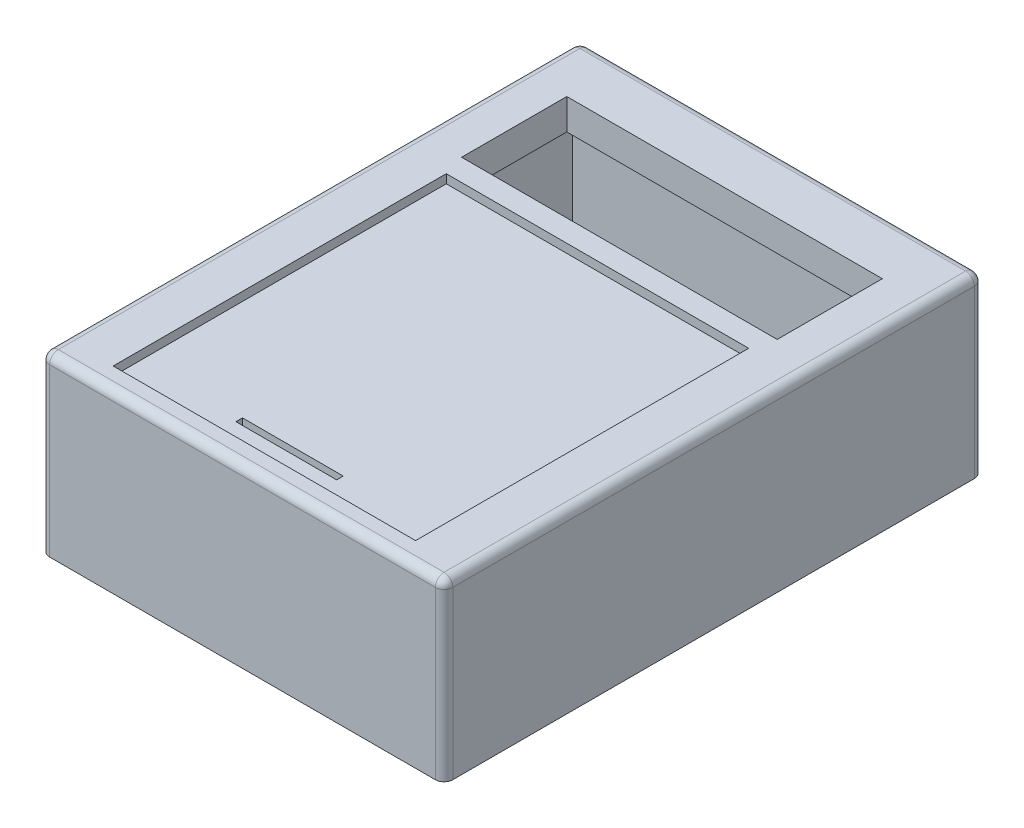
SolidWorks part; units mm, degrees
ref_plane "Front Plane" through (0, 0, 0) normal (0, 0, 1) x (1, 0, 0)
ref_plane "Top Plane" through (0, 0, 0) normal (0, 1, 0) x (1, 0, 0)
ref_plane "Right Plane" through (0, 0, 0) normal (1, 0, 0) x (0, 0, -1)
sketch "Sketch1" plane through (0, 0, 0) normal (0, 1, 0) x (1, 0, 0)
  line L1 (0, 0) -> (92, 0)
  line L2 (0, 0) -> (0, 123)
  line L3 (0, 123) -> (92, 123)
  line L4 (92, 0) -> (92, 123)
  dimension "D1" = 123
  dimension "D2" = 92
extrude "Boss-Extrude1" add sketch "Sketch1" along normal blind 40
sketch "Sketch2" plane through (0, 40, 0) normal (0, 1, 0) x (1, 0, 0)
  line L1 (10, 110) -> (82, 110)
  line L2 (10, 110) -> (10, 86)
  line L3 (10, 86) -> (82, 86)
  line L4 (82, 110) -> (82, 86)
  line L6 (92, 123) -> (0, 123) construction
  point P6 (46, 123)
  point P7 (46, 110)
  dimension "D1" = 72
  dimension "D2" = 24
  dimension "10" = 13
extrude "Cut-Extrude1" cut sketch "Sketch2" against normal through all
sketch "Sketch3" plane through (0, 40, 0) normal (0, 1, 0) x (1, 0, 0)
  line L1 (11.5, 81) -> (80.5, 81)
  line L2 (11.5, 81) -> (11.5, 5)
  line L3 (11.5, 5) -> (80.5, 5)
  line L4 (80.5, 81) -> (80.5, 5)
  line L6 (10, 86) -> (82, 86) construction
  dimension "D1" = 76
  dimension "D2" = 69
  dimension "D4" = 5
extrude "Cut-Extrude2" cut sketch "Sketch3" against normal blind 2
sketch "Sketch5" plane through (0, 38, 0) normal (0, 1, 0) x (1, 0, 0)
  line L1 (34.5, 11.5) -> (57.5, 11.5)
  line L2 (34.5, 11.5) -> (34.5, 10)
  line L3 (34.5, 10) -> (57.5, 10)
  line L4 (57.5, 11.5) -> (57.5, 10)
  line L5 (0, 0) -> (92, 0) construction
  line L6 (11.5, 5) -> (80.5, 5) construction
  point P4 (46, 10)
  point P7 (46, 0)
  dimension "D1" = 23
  dimension "D2" = 1.5
  dimension "D3" = 5
extrude "Cut-Extrude4" cut sketch "Sketch5" against normal through all
fillet "Fillet1" radius 2 8 edges at (92, 20, -123) (0, 20, -123) (0, 20, 0) (92, 20, 0) (0, 40, -61.5) (46, 40, -123) (92, 40, -61.5) (46, 40, 0)
shell "Shell10" thickness 7 removed face at (46, 40, -61.5)
sketch "Sketch8" plane through (0, 0, 0) normal (0, -1, 0) x (1, 0, 0)
  line L1 (87.6988, -117.4086) -> (3.8757, -117.4086)
  line L2 (87.6988, -117.4086) -> (87.6988, -6.9254)
  line L3 (87.6988, -6.9254) -> (3.8757, -6.9254)
  line L4 (3.8757, -117.4086) -> (3.8757, -6.9254)
extrude "Cut-Extrude6" cut sketch "Sketch8" against normal blind 33
